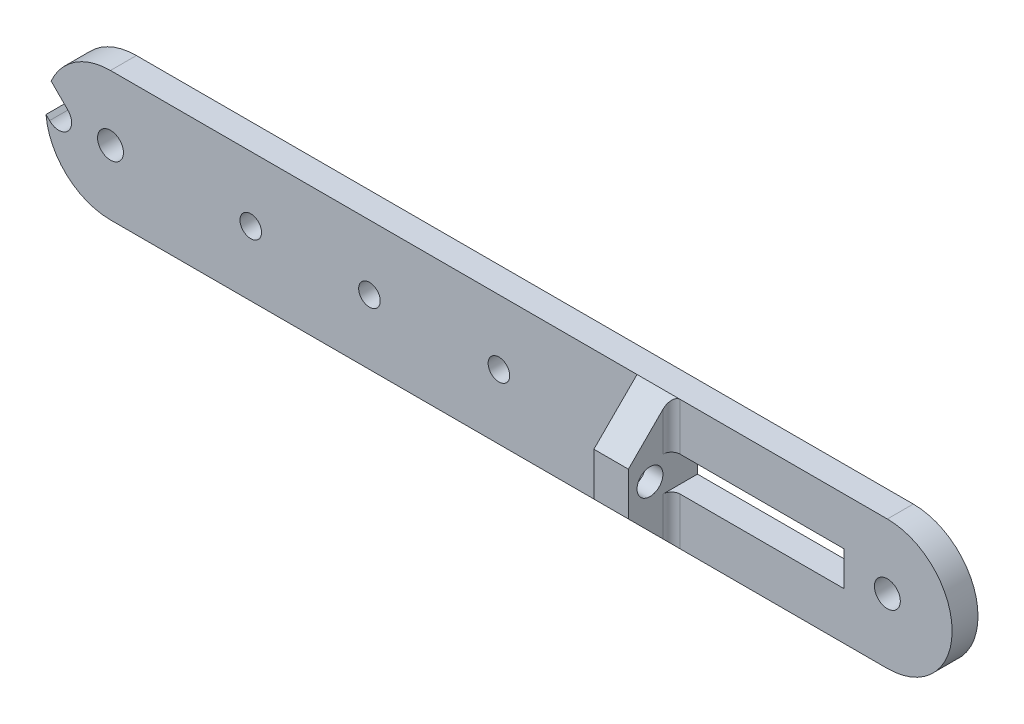
SolidWorks part; units mm, degrees
ref_plane "Plan de face" through (0, 0, 0) normal (0, 0, 1) x (1, 0, 0)
ref_plane "Plan de dessus" through (0, 0, 0) normal (0, 1, 0) x (1, 0, 0)
ref_plane "Plan de droite" through (0, 0, 0) normal (1, 0, 0) x (0, 0, -1)
sketch "Esquisse1" plane through (0, 0, 0) normal (0, 0, 1) x (1, 0, 0)
  line L0 (-74.3787, 0) -> (69.7437, 0) construction
  line L1 (0, 0) -> (0, 19.0596) construction
  line L2 (90, -15) -> (-90, -15)
  line L3 (90, 15) -> (-90, 15)
  line L5 (40, -4) -> (80, -4)
  line L6 (40, -4) -> (40, 4)
  line L7 (40, 4) -> (80, 4)
  line L8 (80, -4) -> (80, 4)
  line L9 (40, -4) -> (80, 4) construction
  line L10 (40, 4) -> (80, -4) construction
  arc A0 (90, -15) -> (90, 15) centre (90, 0) ccw
  circle A1 centre (90, 0) radius 3
  circle A2 centre (-90, 0) radius 3
  arc A3 (-90, -15) -> (-90, 15) centre (-90, 0) cw
  circle A4 centre (0, 0) radius 2.5
  circle A5 centre (-57.5, 0) radius 2.5
  circle A6 centre (-30, 0) radius 2.5
  point P4 (60, 0)
  point P17 (0, -15)
  point P20 (0, 15)
  dimension "D1" = 30
  dimension "D3" = 6
  dimension "D7" = 5
  dimension "D8" = 5
  dimension "D9" = 5
  dimension "D2" = 90
  dimension "D4" = 8
  dimension "D5" = 40
  dimension "D6" = 60
  dimension "D10" = 30
  dimension "D11" = 30
extrude "Boss.-Extru.1" add sketch "Esquisse1" along normal blind 6
sketch "Esquisse2" plane through (40, 0, 0) normal (1, 0, 0) x (0, 0, -1)
  line L0 (0, -4) -> (-6, 4) construction
  line L1 (-6, 4) -> (-6, 0) construction
  line L2 (-6, 4) -> (-6, -4) construction
  line L3 (-6, 0) -> (-15.5036, 0) construction
  line L4 (-6, 15) -> (-6, -15) construction
  line L6 (-16, 5) -> (-16, -5)
  line L8 (-6, 5) -> (-6, -5)
  line L9 (-16, 5) -> (-6, -5) construction
  line L10 (-16, -5) -> (-6, 5) construction
  line L11 (-6, -15) -> (-16, -5)
  line L12 (-6, -15) -> (-6, -5)
  line L13 (-6, 5) -> (-6, 15)
  line L14 (-6, 15) -> (-16, 5)
  circle A0 centre (-11, 0) radius 3
  point P7 (-11, 0)
  dimension "D3" = 6
  dimension "D1" = 10
  dimension "D2" = 10
extrude "Boss.-Extru.2" add sketch "Esquisse2" against normal blind 8
fillet "Congé2" radius 2 2 edges
sketch "Esquisse3" plane through (32, 0, 0) normal (-1, 0, 0) x (0, 0, 1)
  line L0 (11, 0) -> (11, 4) construction
  line L1 (11, 0) -> (14.4641, 2) construction
  line L2 (11, 0) -> (14.4641, -2) construction
  line L3 (11, 4) -> (14.4641, 2)
  line L4 (14.4641, 2) -> (14.4641, -2)
  line L5 (14.4641, -2) -> (11, -4)
  line L6 (7.5359, 2) -> (7.5359, -2)
  line L7 (11, 4) -> (7.5359, 2)
  line L8 (7.5359, -2) -> (11, -4)
  dimension "D2" = 60
  dimension "D3" = 60
extrude "Enlèv. mat.-Extru.1" cut sketch "Esquisse3" against normal blind 4
sketch "Esquisse4" plane through (0, 0, 6) normal (0, 0, 1) x (1, 0, 0)
  line L0 (-90, 0) -> (-105, 0) construction
  line L1 (-105, 0) -> (-102, 0) construction
  line L2 (-102, 0) -> (-104.1213, -2.1213) construction
  line L3 (-104.1213, -2.1213) -> (-99.8787, 2.1213)
  line L4 (-104.1213, -2.1213) -> (-99.8787, 2.1213)
  line L5 (-104.1213, -2.1213) -> (-108.504, 2.2614)
  line L6 (-99.8787, 2.1213) -> (-104.2614, 6.504)
  line L7 (-108.504, 2.2614) -> (-104.2614, 6.504)
  arc A0 (-90, 15) -> (-90, -15) centre (-90, 0) ccw construction
  circle A1 centre (-102, 0) radius 3
  arc M9 (-90, 15) -> (-90, -15) centre (-90, 0) ccw
  dimension "D1" = 3
  dimension "D2" = 45
extrude "Enlèv. mat.-Extru.4" cut sketch "Esquisse4" against normal blind 10 contours L3 A1 | A1 L6 M9 | A1 L5 M9 | L3 A1 region at (-102.9003, 0.9003, 6) region at (-101.0997, -0.9003, 6) region at (-104.7977, -1.1965, 6) region at (-103.2777, 3.6386, 6)
